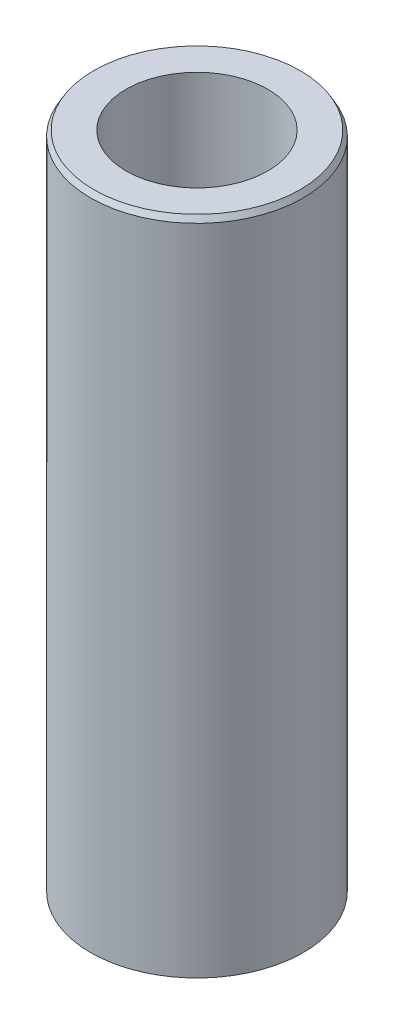
SolidWorks part; units mm, degrees
ref_plane "Front Plane" through (0, 0, 0) normal (0, 0, 1) x (1, 0, 0)
ref_plane "Top Plane" through (0, 0, 0) normal (0, 1, 0) x (1, 0, 0)
ref_plane "Right Plane" through (0, 0, 0) normal (1, 0, 0) x (0, 0, -1)
sketch "Sketch1" plane through (0, 0, 0) normal (0, 1, 0) x (1, 0, 0)
  circle A0 centre (0, 0) radius 37.5
  dimension "SHAFT_OD" = 75
extrude "Boss-Extrude1" add sketch "Sketch1" along normal blind 233.5075
sketch "Sketch2" plane through (0, 0, 0) normal (0, 1, 0) x (1, 0, 0)
  circle A0 centre (0, 0) radius 24.9844
  dimension "BORE_D" = 49.9688
extrude "Cut-Extrude1" cut sketch "Sketch2" along normal through all
chamfer "Chamfer1" distance 1.9564 angle 30 2 edges at (0, 233.5075, 37.5) (0, 0, 37.5) first distance on face at (0, 233.5075, 37.5) first distance on face at (0, 0, 24.9844)
